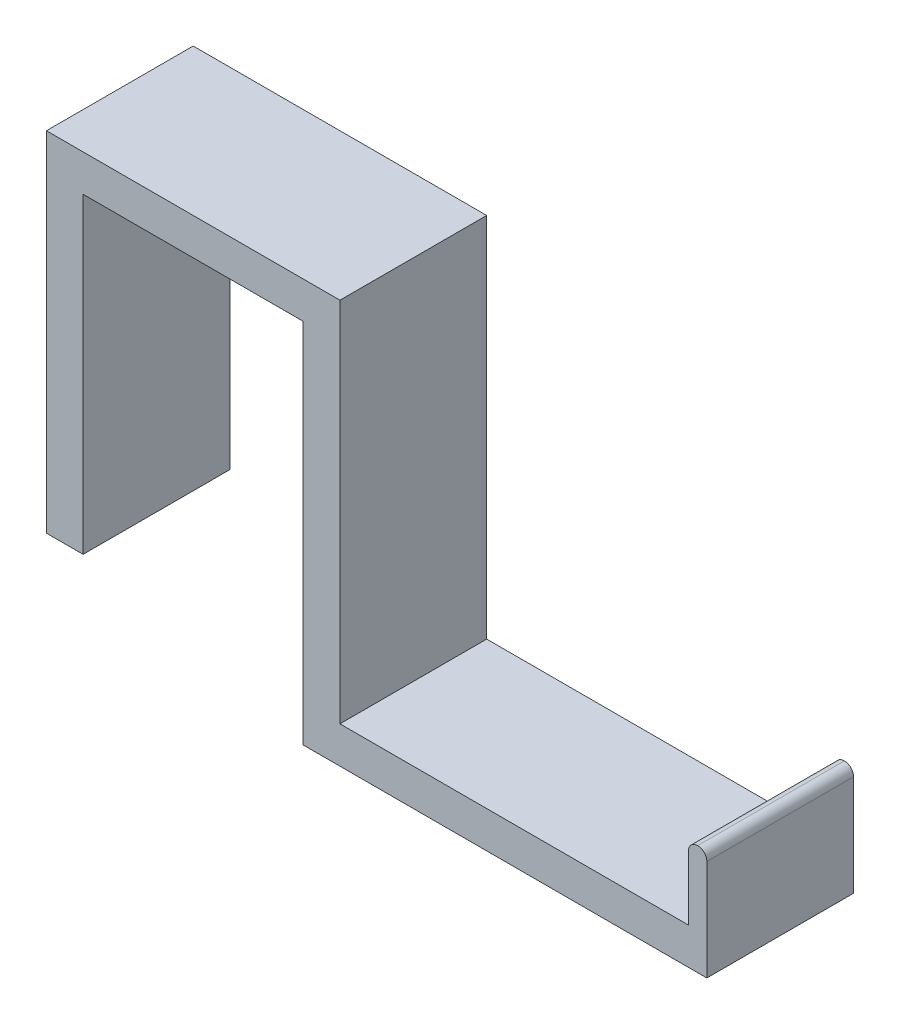
SolidWorks part; units mm, degrees
ref_plane "前基準面" through (0, 0, 0) normal (0, 0, 1) x (1, 0, 0)
ref_plane "上基準面" through (0, 0, 0) normal (0, 1, 0) x (1, 0, 0)
ref_plane "右基準面" through (0, 0, 0) normal (1, 0, 0) x (0, 0, -1)
sketch "草圖1" plane through (0, 0, 0) normal (0, 0, 1) x (1, 0, 0)
  line L0 (-39.7324, -56.4062) -> (-29.7324, -56.4062)
  line L1 (-39.7324, 33.5938) -> (-29.7324, 33.5938)
  line L2 (-39.7324, 33.5938) -> (-39.7324, -56.4062)
  line L4 (-29.7324, 33.5938) -> (-29.7324, -56.4062)
  line L14 (-39.7324, -56.4062) -> (70.2676, -56.4062)
  line L15 (-39.7324, -56.4062) -> (-39.7324, -66.4062)
  line L16 (-39.7324, -66.4062) -> (70.2676, -66.4062)
  line L17 (70.2676, -56.4062) -> (70.2676, -66.4062)
  line L18 (65.2676, -56.4062) -> (70.2676, -56.4062)
  line L19 (65.2676, -56.4062) -> (65.2676, -36.4062)
  line L20 (65.2676, -36.4062) -> (70.2676, -36.4062)
  line L21 (70.2676, -56.4062) -> (70.2676, -36.4062)
  line L26 (-29.7324, 33.5938) -> (-109.7324, 33.5938)
  line L27 (-29.7324, 33.5938) -> (-29.7324, 43.5938)
  line L28 (-29.7324, 43.5938) -> (-109.7324, 43.5937)
  line L29 (-109.7324, 33.5938) -> (-109.7324, 43.5937)
  line L30 (-109.7324, 33.5938) -> (-99.7324, 33.5938)
  line L31 (-109.7324, 33.5938) -> (-109.7324, -51.4063)
  line L32 (-109.7324, -51.4063) -> (-99.7324, -51.4063)
  line L33 (-99.7324, 33.5938) -> (-99.7324, -51.4063)
  dimension "D1" = 10
  dimension "D2" = 90
  dimension "D3" = 10
  dimension "D4" = 110
  dimension "D5" = 5
  dimension "D6" = 20
  dimension "D7" = 10
  dimension "D8" = 80
  dimension "D9" = 85
  dimension "D10" = 10
extrude "填料-伸長1" add sketch "草圖1" along normal blind 40 contours L4 L1 L2 L0 | L17 L14 L0 L15 L16 | L26 L29 L28 L27 | L21 L20 L19 L18 | L31 L30 L33 L32 region at (-34.7324, -11.4062, 0) region at (15.2676, -61.4062, 0)
fillet "圓角1" radius 2.5 2 edges at (70.2676, -36.4062, 20) (65.2676, -36.4062, 20)
